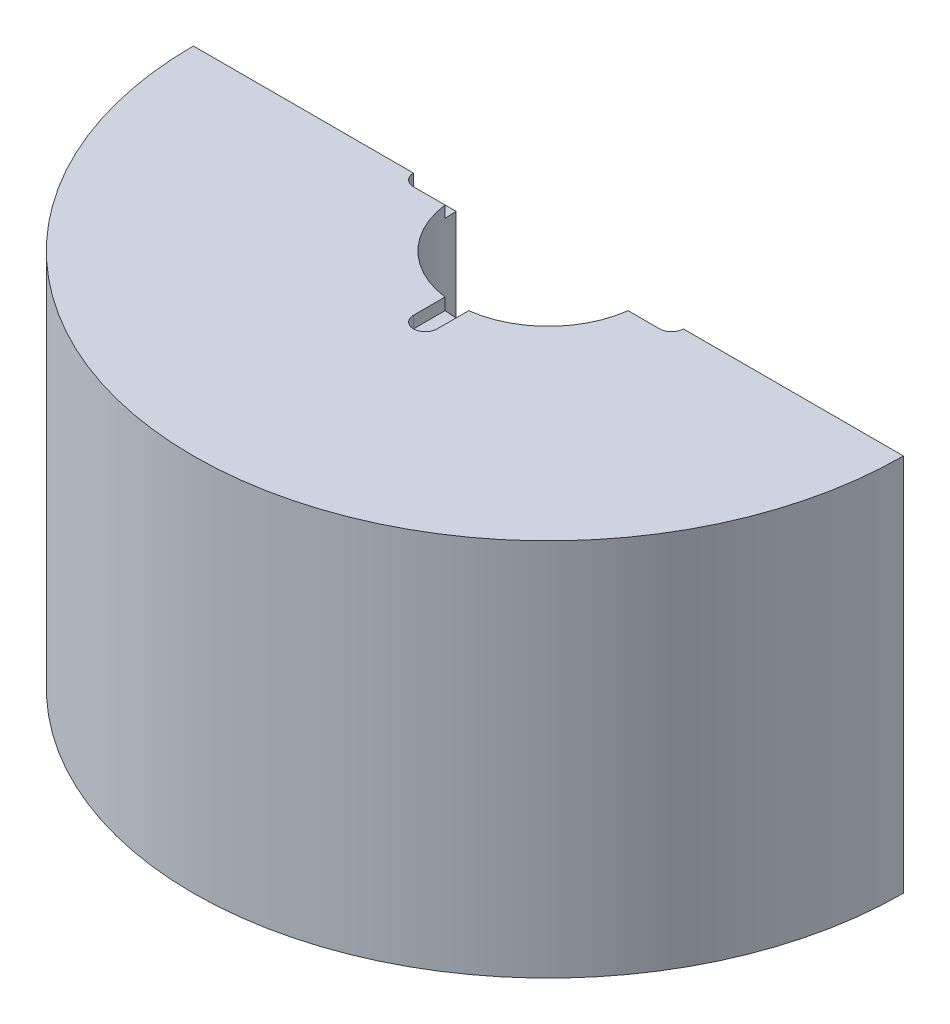
SolidWorks part; units mm, degrees
ref_plane "Front Plane" through (0, 0, 0) normal (0, 0, 1) x (1, 0, 0)
ref_plane "Top Plane" through (0, 0, 0) normal (0, 1, 0) x (1, 0, 0)
ref_plane "Right Plane" through (0, 0, 0) normal (1, 0, 0) x (0, 0, -1)
sketch "Sketch1" plane through (0, 0, 0) normal (0, 1, 0) x (1, 0, 0)
  line L0 (-150, 0) -> (150, 0)
  circle A0 centre (0, 0) radius 150
  circle A2 centre (0, 0) radius 39
extrude "Boss-Extrude1" add sketch "Sketch1" along normal blind 160 contours A2 L0 A0 region at (0, 0, 67.0775)
sketch "Sketch2" plane through (0, 160, 0) normal (0, 1, 0) x (1, 0, 0)
  line L0 (0, 0) -> (0, -52)
  line L1 (-52, 5) -> (-35.0738, 5)
  line L2 (-5, -52) -> (5, -52)
  line L3 (-5, -52) -> (-5, -35.0738)
  line L4 (-5, -35.0738) -> (5, -35.0738)
  line L5 (5, -52) -> (5, -35.0738)
  line L6 (-52, 5) -> (-52, -5)
  line L7 (-52, -5) -> (-35.0738, -5)
  line L8 (-35.0738, 5) -> (-35.0738, -5)
  line L9 (5, 52) -> (5, 35.0738)
  line L10 (5, 52) -> (-5, 52)
  line L11 (-5, 52) -> (-5, 35.0738)
  line L12 (5, 35.0738) -> (-5, 35.0738)
  line L13 (52, -5) -> (35.0738, -5)
  line L14 (52, -5) -> (52, 5)
  line L15 (52, 5) -> (35.0738, 5)
  line L16 (35.0738, -5) -> (35.0738, 5)
  circle A0 centre (0, 0) radius 39
  circle A1 centre (0, -52) radius 5
  circle A2 centre (-52, 0) radius 5
  circle A3 centre (0, 52) radius 5
  circle A4 centre (52, 0) radius 5
  point P30 (0, 0)
  arc M2 (39, 0) -> (-39, 0) centre (0, 0) cw
  line M3 (-39, 0) -> (-150, 0)
  line M5 (150, 0) -> (39, 0)
  dimension "D1" = 4
extrude "Cut-Extrude1" cut sketch "Sketch2" against normal blind 5 contours A2 L7 M2 M3 | A2 A0 L1 M3 | L6 A2 M3 | A2 L6 M3 | L6 A2 M3 | A2 L6 M3 | A4 L15 A0 M5 | A4 L13 M5 M2 | A4 L14 M5 | L14 A4 M5 | A4 L14 M5 | L14 A4 M5 | A1 | L5 L4 L3 L2 region at (-43.5503, 160, 2.6763) region at (43.5503, 160, 2.6763) region at (-54.1221, 160, 2.1221) region at (-49.8779, 160, 2.1221) region at (-43.5503, 160, -2.6763) region at (49.8779, 160, 2.1221) region at (54.1221, 160, 2.1221) region at (43.5503, 160, -2.6763) region at (-54.1221, 160, -2.1221) region at (-49.8779, 160, -2.1221) region at (49.8779, 160, -2.1221) region at (54.1221, 160, -2.1221)
extrude "Cut-Extrude2" cut sketch "Sketch2<3>" along normal blind 5 from offset 160 contours A2 | L7 L8 L1 L6 | L3 L4 L5 L2 | A1 | L13 L16 L15 L14 | A4 offset against normal yes
sketch "Sketch2<3>" plane through (0, 160, 0) normal (0, 1, 0) x (1, 0, 0) same geometry as "Sketch2"
